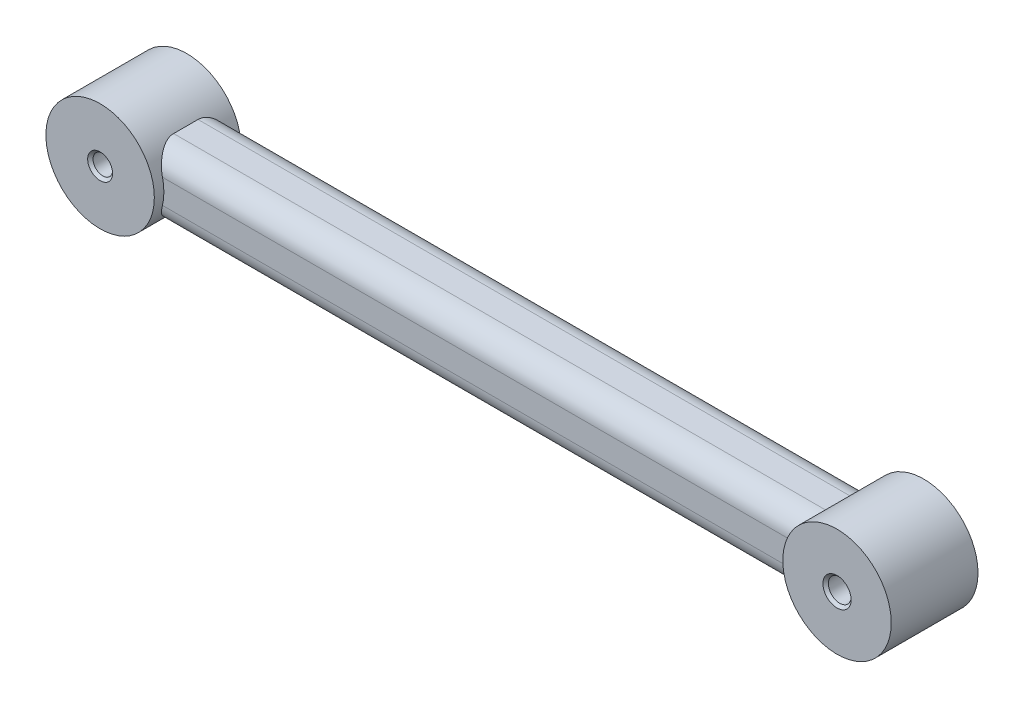
SolidWorks part; units mm, degrees
material "高韧性光敏树脂"
ref_plane "前视基准面" through (0, 0, 0) normal (0, 0, 1) x (1, 0, 0)
ref_plane "上视基准面" through (0, 0, 0) normal (0, 1, 0) x (1, 0, 0)
ref_plane "右视基准面" through (0, 0, 0) normal (1, 0, 0) x (0, 0, -1)
sketch "草图1" plane through (0, 0, 0) normal (0, 0, 1) x (1, 0, 0)
  circle A0 centre (0, 0) radius 2
  circle A1 centre (27.1807, 0) radius 2
  circle A2 centre (0, 0) radius 0.36
  circle A3 centre (27.1807, 0) radius 0.42
  dimension "D1" = 4
  dimension "D2" = 4
  dimension "D3" = 0.84
  dimension "D4" = 0.72
  dimension "D5" = 27.1807
extrude "凸台-拉伸1" add sketch "草图1" along normal mid plane 3.2
ref_plane "基准面1" through (3, 0, 0) normal (1, 0, 0) x (0, 0, -1)
sketch "草图2" plane through (3, 0, 0) normal (1, 0, 0) x (0, 0, -1)
  line L1 (-1.25, -1.25) -> (1.25, -1.25)
  line L2 (-1.25, -1.25) -> (-1.25, 1.25)
  line L3 (-1.25, 1.25) -> (1.25, 1.25)
  line L4 (1.25, -1.25) -> (1.25, 1.25)
  line L5 (-1.25, -1.25) -> (1.25, 1.25) construction
  line L6 (-1.25, 1.25) -> (1.25, -1.25) construction
  point P0 (0, 0)
  dimension "D1" = 2.5
extrude "凸台-拉伸2" add sketch "草图2" along normal up to surface and the other way up to surface contours L1 L4 L3 L2 region at (3, 0, 0) up to face at (29.1807, 0, 1.6) other way up to face at (2, 0, 1.6)
chamfer "倒角1" distance 0.1 angle 45 4 edges at (27.6007, 0, 1.6) (27.6007, 0, -1.6) (0.36, 0, 1.6) (0.36, 0, -1.6)
fillet "圆角1" radius 0.8 4 edges at (13.5904, -1.25, 1.25) (13.5904, -1.25, -1.25) (13.5904, 1.25, 1.25) (13.5904, 1.25, -1.25)
